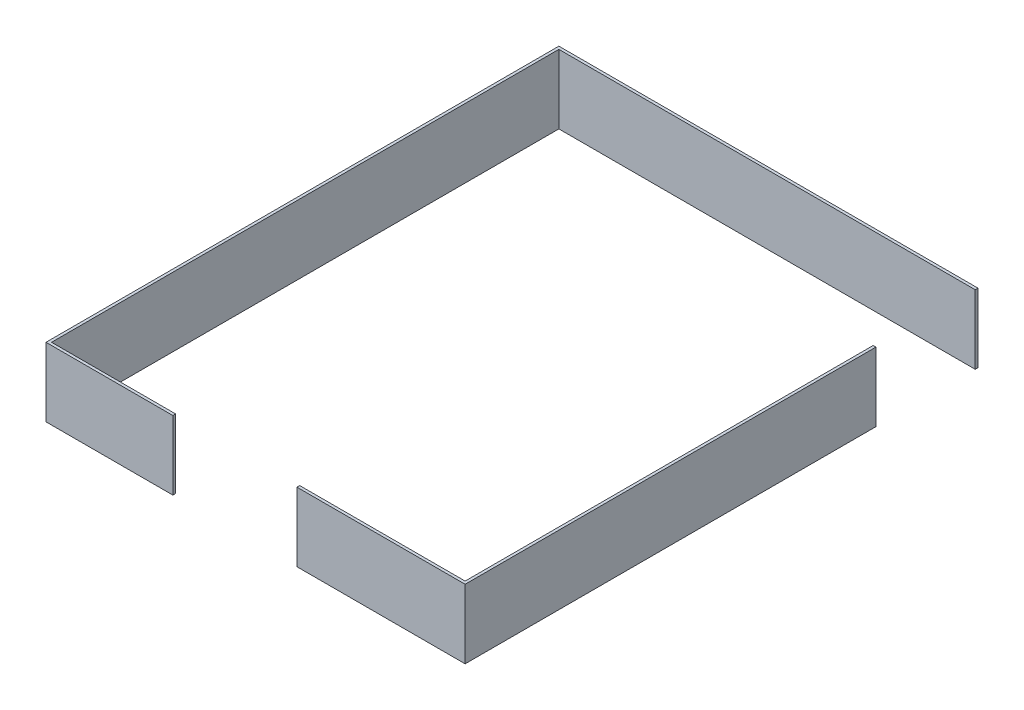
SolidWorks part; units mm, degrees
ref_plane "Front Plane" through (0, 0, 0) normal (0, 0, 1) x (1, 0, 0)
ref_plane "Top Plane" through (0, 0, 0) normal (0, 1, 0) x (1, 0, 0)
ref_plane "Right Plane" through (0, 0, 0) normal (1, 0, 0) x (0, 0, -1)
sketch "Sketch2" plane through (0, 0, 0) normal (0, 1, 0) x (1, 0, 0)
  line L1 (0, 0) -> (610, 0)
  line L2 (0, 0) -> (0, -10)
  line L3 (0, -10) -> (610, -10)
  line L4 (610, 0) -> (610, -10)
  line L5 (600, 1480) -> (610, 1480)
  line L6 (600, 1480) -> (600, 0)
  line L8 (610, 1480) -> (610, 0)
  line L9 (-450, -10) -> (-910, -10)
  line L10 (-450, -10) -> (-450, 0)
  line L11 (-450, 0) -> (-910, 0)
  line L12 (-910, -10) -> (-910, 0)
  line L13 (-900, 1850) -> (-910, 1850)
  line L14 (-900, 1850) -> (-900, 0)
  line L16 (-910, 1850) -> (-910, 0)
  line L17 (610, 1840) -> (-900, 1840)
  line L18 (610, 1840) -> (610, 1850)
  line L19 (610, 1850) -> (-900, 1850)
  point P17 (-2010.1104, 1208.9203)
  dimension "D1" = 610
  dimension "D2" = 10
  dimension "D3" = 1480
  dimension "D4" = 10
  dimension "D5" = 450
  dimension "D6" = 460
  dimension "D7" = 10
  dimension "D8" = 10
  dimension "D9" = 1850
  dimension "D10" = 1510
  dimension "D11" = 10
extrude "Boss-Extrude2" add sketch "Sketch2" along normal blind 250 contours L11 L10 L9 L12
extrude "Boss-Extrude3" add sketch "Sketch2<11>" along normal blind 250 contours L13 L16 L11 L14 region at (-905, 0, -925)
sketch "Sketch2<11>" plane through (0, 0, 0) normal (0, 1, 0) x (1, 0, 0) same geometry as "Sketch2"
extrude "Boss-Extrude4" add sketch "Sketch2<12>" along normal blind 250 separate body contours L4 L1 L2 L3 region at (305, 0, 5)
sketch "Sketch2<12>" plane through (0, 0, 0) normal (0, 1, 0) x (1, 0, 0) same geometry as "Sketch2"
extrude "Boss-Extrude5" add sketch "Sketch2<14>" along normal blind 250 contours L8 L5 L6 L1 region at (605, 0, -740)
sketch "Sketch2<14>" plane through (0, 0, 0) normal (0, 1, 0) x (1, 0, 0) same geometry as "Sketch2"
extrude "Boss-Extrude6" add sketch "Sketch2<15>" along normal blind 250 contours L18 L19 L14 L17 region at (-145, 0, -1845)
sketch "Sketch2<15>" plane through (0, 0, 0) normal (0, 1, 0) x (1, 0, 0) same geometry as "Sketch2"
